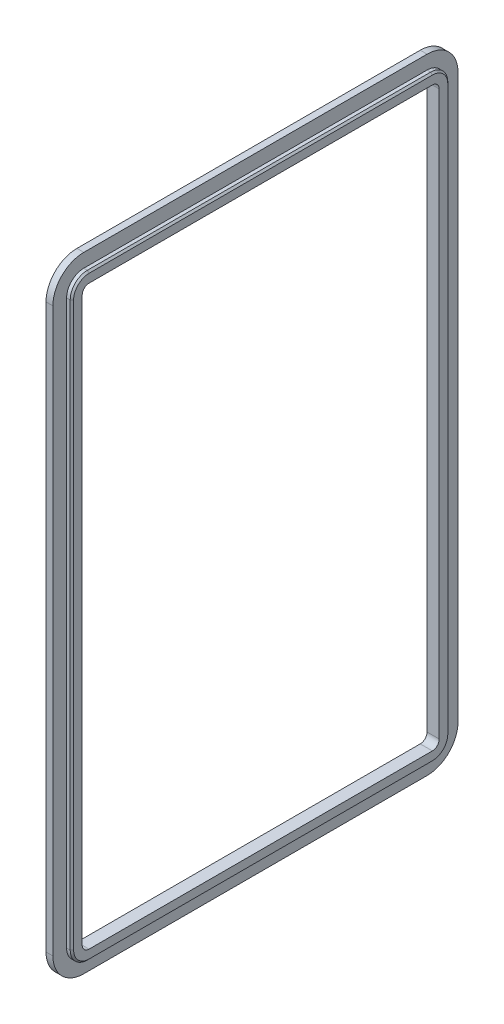
SolidWorks part; units mm, degrees
ref_plane "Front Plane" through (0, 0, 0) normal (1, 0, 0) x (0, 1, 0)
ref_plane "Top Plane" through (0, 0, 0) normal (0, 0, 1) x (0, 1, 0)
ref_plane "Right Plane" through (0, 0, 0) normal (0, 1, 0) x (-1, 0, 0)
sketch "Sketch2" plane through (0, 0, 0) normal (-1, 0, 0) x (0, 0, 1)
  line L5 (0, -43.5) -> (0, 43.5) construction
  line L11 (-27.5, 41) -> (-27.5, -41)
  line L12 (25, 43.5) -> (-25, 43.5)
  line L13 (27.5, -41) -> (27.5, 41)
  line L14 (-25, -43.5) -> (25, -43.5)
  line L15 (-27.5, 41) -> (-27.5, -41)
  line L16 (25, 43.5) -> (-25, 43.5)
  line L17 (27.5, -41) -> (27.5, 41)
  line L18 (-25, -43.5) -> (25, -43.5)
  arc A4 (-27.5, -41) -> (-25, -43.5) centre (-25, -41) ccw
  arc A5 (-25, 43.5) -> (-27.5, 41) centre (-25, 41) ccw
  arc A6 (27.5, 41) -> (25, 43.5) centre (25, 41) ccw
  arc A7 (25, -43.5) -> (27.5, -41) centre (25, -41) ccw
  arc A8 (-27.5, -41) -> (-25, -43.5) centre (-25, -41) ccw
  arc A9 (-25, 43.5) -> (-27.5, 41) centre (-25, 41) ccw
  arc A10 (27.5, 41) -> (25, 43.5) centre (25, 41) ccw
  arc A11 (25, -43.5) -> (27.5, -41) centre (25, -41) ccw
  dimension "D1" = 0
extrude "Boss-Extrude1" add sketch "Sketch2" against normal offset from surface (0.77 mm away) 0.5 contours A8 L18 A11 L17 A10 L16 A9 L15
sketch "Sketch3" plane through (0, 0, 0) normal (-1, 0, 0) x (0, 0, 1)
  line L8 (-29.5, 41) -> (-29.5, -41)
  line L9 (-25, -45.5) -> (25, -45.5)
  line L10 (29.5, -41) -> (29.5, 41)
  line L11 (25, 45.5) -> (-25, 45.5)
  line L12 (-29.5, 41) -> (-29.5, -41)
  line L13 (-25, -45.5) -> (25, -45.5)
  line L14 (29.5, -41) -> (29.5, 41)
  line L15 (25, 45.5) -> (-25, 45.5)
  line L20 (-26, 41) -> (-26, -41)
  line L21 (-25, -42) -> (25, -42)
  line L22 (26, -41) -> (26, 41)
  line L23 (25, 42) -> (-25, 42)
  line L24 (-26, 41) -> (-26, -41)
  line L25 (-25, -42) -> (25, -42)
  line L26 (26, -41) -> (26, 41)
  line L27 (25, 42) -> (-25, 42)
  arc A8 (-29.5, -41) -> (-25, -45.5) centre (-25, -41) ccw
  arc A9 (25, -45.5) -> (29.5, -41) centre (25, -41) ccw
  arc A10 (29.5, 41) -> (25, 45.5) centre (25, 41) ccw
  arc A11 (-25, 45.5) -> (-29.5, 41) centre (-25, 41) ccw
  arc A12 (-29.5, -41) -> (-25, -45.5) centre (-25, -41) ccw
  arc A13 (25, -45.5) -> (29.5, -41) centre (25, -41) ccw
  arc A14 (29.5, 41) -> (25, 45.5) centre (25, 41) ccw
  arc A15 (-25, 45.5) -> (-29.5, 41) centre (-25, 41) ccw
  arc A20 (-26, -41) -> (-25, -42) centre (-25, -41) ccw
  arc A21 (25, -42) -> (26, -41) centre (25, -41) ccw
  arc A22 (26, 41) -> (25, 42) centre (25, 41) ccw
  arc A23 (-25, 42) -> (-26, 41) centre (-25, 41) ccw
  arc A24 (-26, -41) -> (-25, -42) centre (-25, -41) ccw
  arc A25 (25, -42) -> (26, -41) centre (25, -41) ccw
  arc A26 (26, 41) -> (25, 42) centre (25, 41) ccw
  arc A27 (-25, 42) -> (-26, 41) centre (-25, 41) ccw
  line M17 (-27.5, 41) -> (-27.5, -41)
  arc M18 (-27.5, -41) -> (-25, -43.5) centre (-25, -41) ccw
  line M19 (-25, -43.5) -> (25, -43.5)
  arc M20 (25, -43.5) -> (27.5, -41) centre (25, -41) ccw
  line M21 (27.5, -41) -> (27.5, 41)
  arc M22 (27.5, 41) -> (25, 43.5) centre (25, 41) ccw
  line M23 (25, 43.5) -> (-25, 43.5)
  arc M24 (-25, 43.5) -> (-27.5, 41) centre (-25, 41) ccw
  dimension "D1" = 2
  dimension "D2" = 1.5
extrude "Boss-Extrude2" add sketch "Sketch3" along normal blind 1 contours L15 A15 L12 A12 L13 A13 L14 A14 M17 M24 M23 M22 M21 M20 M19 M18 | A27 L27 A26 L26 A25 L25 A24 L24 M24 M17 M18 M19 M20 M21 M22 M23 | L12 A12 L13 A13 L14 A14 L15 A15 region at (0, 43.4151, -27.4151) region at (0, 42.04, -26.04)
extrude "Cut-Extrude1" cut sketch "Sketch3<3>" against normal through all both and the other way through all contours L27 A27 L24 A24 L25 A25 L26 A26 region at (0, 0, 0)
sketch "Sketch3<3>" plane through (0, 0, 0) normal (-1, 0, 0) x (0, 0, 1) same geometry as "Sketch3"
chamfer "Chamfer1" distance 0.25 angle 45 8 edges at (0.77, 43.5, 0) (0.77, 42.7678, 26.7678) (0.77, 42.7678, -26.7678) (0.77, 0, 27.5) (0.77, 0, -27.5) (0.77, -42.7678, 26.7678) (0.77, -42.7678, -26.7678) (0.77, -43.5, 0)
